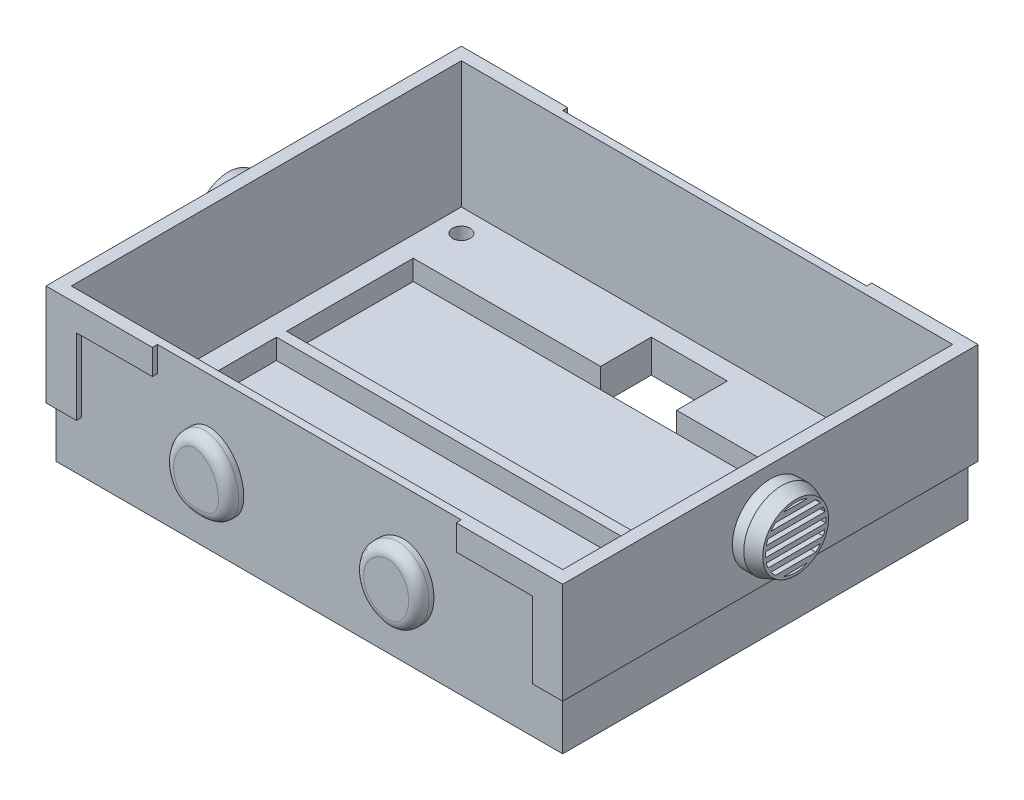
SolidWorks part; units mm, degrees
ref_plane "Plan de face" through (0, 0, 0) normal (0, 0, 1) x (1, 0, 0)
ref_plane "Plan de dessus" through (0, 0, 0) normal (0, 1, 0) x (1, 0, 0)
ref_plane "Plan de droite" through (0, 0, 0) normal (1, 0, 0) x (0, 0, -1)
sketch "Esquisse1" plane through (0, 0, 0) normal (0, 1, 0) x (1, 0, 0)
  line L1 (0, 0) -> (100, 0)
  line L2 (0, 0) -> (0, 80)
  line L3 (0, 80) -> (100, 80)
  line L4 (100, 0) -> (100, 80)
  line L13 (42.5, 75) -> (57.5, 75)
  line L14 (42.5, 75) -> (42.5, 65)
  line L15 (42.5, 65) -> (57.5, 65)
  line L16 (57.5, 75) -> (57.5, 65)
  dimension "D1" = 80
  dimension "D2" = 100
  dimension "D11" = 15
  dimension "D12" = 10
  dimension "D13" = 42.5
  dimension "D14" = 5
extrude "Boss.-Extru.2" add sketch "Esquisse1" along normal blind 5
sketch "Esquisse2" plane through (0, 5, 0) normal (0, 1, 0) x (1, 0, 0)
  line L0 (1.5, 10.5) -> (1.5, 1.5)
  line L1 (0, 80) -> (100, 80)
  line L2 (0, 80) -> (0, 68.5)
  line L3 (0, 0) -> (100, 0)
  line L4 (100, 80) -> (100, 0)
  line L5 (1.5, 78.5) -> (98.5, 78.5)
  line L6 (1.5, 78.5) -> (1.5, 69.5)
  line L7 (1.5, 1.5) -> (98.5, 1.5)
  line L8 (98.5, 78.5) -> (98.5, 1.5)
  line L9 (1.5, 10.5) -> (1.5, 69.5)
  line L10 (0, 68.5) -> (0, 13)
  line L18 (0, 13) -> (0, 0)
  dimension "D1" = 1.5
  dimension "D2" = 1.5
  dimension "D3" = 1.5
  dimension "D4" = 1.5
  dimension "D7" = 9
extrude "Boss.-Extru.3" add sketch "Esquisse2" along normal blind 25
sketch "Esquisse9" plane through (0, 0, 0) normal (0, -1, 0) x (1, 0, 0)
  line L0 (100, 0) -> (100, -80) construction
  line L1 (89, -2) -> (11, -2)
  line L2 (98, -11) -> (98, -69)
  line L3 (89, -78) -> (11, -78)
  line L4 (2, -11) -> (2, -69)
  line L5 (0, 0) -> (100, 0) construction
  line L6 (0, -80) -> (0, 0) construction
  line L7 (100, -80) -> (0, -80) construction
  line L9 (57.5, -65) -> (42.5, -65)
  line L10 (57.5, -65) -> (57.5, -75)
  line L11 (57.5, -75) -> (42.5, -75)
  line L12 (42.5, -65) -> (42.5, -75)
  line L15 (98, -11) -> (89, -11)
  line L16 (89, -2) -> (89, -11)
  line L19 (2, -11) -> (11, -11)
  line L20 (11, -2) -> (11, -11)
  line L23 (98, -69) -> (89, -69)
  line L24 (89, -78) -> (89, -69)
  line L27 (2, -69) -> (11, -69)
  line L28 (11, -78) -> (11, -69)
  dimension "D1" = 2
  dimension "D2" = 2
  dimension "D3" = 2
  dimension "D4" = 2
  dimension "D5" = 9
  dimension "D6" = 9
  dimension "D7" = 9
  dimension "D8" = 9
  dimension "D9" = 9
  dimension "D10" = 9
  dimension "D11" = 9
  dimension "D12" = 9
extrude "Boss.-Extru.5" add sketch "Esquisse9" along normal blind 1.5
sketch "Esquisse11" plane through (0, 5, 0) normal (0, 1, 0) x (1, 0, 0)
  line L1 (76.5, 65) -> (5.5, 65)
  line L2 (76.5, 60) -> (76.5, 40)
  line L3 (76.5, 40) -> (5.5, 40)
  line L5 (1.5, 1.5) -> (98.5, 1.5) construction
  line L6 (76.5, 38) -> (5.5, 38)
  line L7 (76.5, 33) -> (76.5, 13)
  line L8 (76.5, 13) -> (5.5, 13)
  line L10 (5.5, 65) -> (5.5, 40)
  line L11 (5.5, 13) -> (5.5, 38)
  line L15 (76.5, 65) -> (84.5, 65)
  line L19 (76.5, 60) -> (84.5, 60)
  line L20 (84.5, 65) -> (84.5, 60)
  line L21 (76.5, 38) -> (84.5, 38)
  line L23 (76.5, 33) -> (84.5, 33)
  line L24 (84.5, 38) -> (84.5, 33)
  dimension "D2" = 71
  dimension "D3" = 25
  dimension "D4" = 25
  dimension "D5" = 11.5
  dimension "D6" = 2
  dimension "D7" = 71
  dimension "D8" = 8
  dimension "D9" = 8
  dimension "D10" = 5
  dimension "D11" = 5
extrude "Enlèv. mat.-Extru.4" cut sketch "Esquisse11" against normal blind 4
sketch "Esquisse12" plane through (0, 5, 0) normal (0, 1, 0) x (1, 0, 0)
  line L0 (1.5, 78.5) -> (98.5, 78.5) construction
  line L1 (1.5, 1.5) -> (1.5, 78.5) construction
  line L2 (98.5, 78.5) -> (98.5, 1.5) construction
  line L3 (98.5, 1.5) -> (1.5, 1.5) construction
  line L4 (1.5, 1.5) -> (1.5, 78.5) construction
  circle A0 centre (6, 74) radius 1.75
  circle A1 centre (94, 74) radius 1.75
  circle A2 centre (94, 6) radius 1.75
  circle A3 centre (6, 6) radius 1.75
  dimension "D1" = 3.5
  dimension "D2" = 4.5
  dimension "D3" = 4.5
  dimension "D4" = 3.5
  dimension "D5" = 4.5
  dimension "D6" = 4.5
  dimension "D7" = 3.5
  dimension "D8" = 4.5
  dimension "D9" = 4.5
  dimension "D10" = 3.5
  dimension "D11" = 4.5
  dimension "D12" = 4.5
extrude "Enlèv. mat.-Extru.5" cut sketch "Esquisse12" against normal blind 10
fillet "Congé1" radius 10 2 edges at (84.5, 1, -62.5) (84.5, 1, -35.5)
sketch "Esquisse13" plane through (0, 0, 0) normal (0, 0, 1) x (1, 0, 0)
  line L0 (100, 30) -> (100, 0) construction
  line L1 (5, 10) -> (0, 10)
  line L2 (5, 10) -> (5, 25)
  line L3 (2.889, 30) -> (0, 30)
  line L4 (0, 10) -> (0, 30)
  line L5 (2.889, 30) -> (20, 30)
  line L7 (5, 25) -> (20, 25)
  line L8 (20, 30) -> (20, 25)
  line L9 (100, 10) -> (95, 10)
  line L10 (100, 10) -> (100, 30)
  line L11 (100, 30) -> (96.2257, 30)
  line L12 (95, 10) -> (95, 25)
  line L13 (0, 30) -> (100, 30) construction
  line L15 (96.2257, 30) -> (80, 30)
  line L17 (95, 25) -> (80, 25)
  line L18 (80, 30) -> (80, 25)
  dimension "D1" = 15
  dimension "D2" = 15
  dimension "D3" = 5
  dimension "D4" = 5
  dimension "D5" = 5
  dimension "D6" = 5
  dimension "D7" = 15
  dimension "D8" = 15
extrude "Boss.-Extru.6" add sketch "Esquisse13" along normal blind 1
sketch "Esquisse14" plane through (0, 0, -80) normal (0, 0, -1) x (-1, 0, 0)
  line L0 (-100, 30) -> (-100, 10)
  line L1 (-100, 30) -> (-100, 0) construction
  line L2 (-100, 10) -> (-95, 10)
  line L3 (-95, 10) -> (-95, 25)
  line L4 (-95, 25) -> (-80, 25)
  line L5 (-80, 25) -> (-80, 30)
  line L6 (-100, 30) -> (0, 30) construction
  line L7 (-80, 30) -> (-100, 30)
  line L8 (0, 30) -> (-20, 30)
  line L9 (-20, 30) -> (-20, 25)
  line L10 (-20, 25) -> (-5, 25)
  line L11 (-5, 25) -> (-5, 10)
  line L12 (-5, 10) -> (0, 10)
  line L13 (0, 30) -> (0, 0) construction
  line L14 (0, 10) -> (0, 30)
  dimension "D1" = 5
  dimension "D2" = 5
  dimension "D3" = 15
  dimension "D4" = 15
  dimension "D5" = 5
  dimension "D6" = 5
  dimension "D7" = 15
  dimension "D8" = 15
extrude "Boss.-Extru.7" add sketch "Esquisse14" along normal blind 1
sketch "Esquisse15" plane through (0, 0, 0) normal (-1, 0, 0) x (0, 0, 1)
  line L1 (-81, 30) -> (1, 30)
  line L2 (-81, 30) -> (-81, 10)
  line L3 (-81, 10) -> (1, 10)
  line L4 (1, 30) -> (1, 10)
extrude "Boss.-Extru.8" add sketch "Esquisse15" along normal blind 1
sketch "Esquisse16" plane through (100, 0, 0) normal (1, 0, 0) x (0, 0, -1)
  line L1 (-1, 30) -> (81, 30)
  line L2 (-1, 30) -> (-1, 10)
  line L3 (-1, 10) -> (81, 10)
  line L4 (81, 30) -> (81, 10)
extrude "Boss.-Extru.9" add sketch "Esquisse16" along normal blind 1
sketch "Esquisse17" plane through (0, 0, 0) normal (0, 0, 1) x (1, 0, 0)
  spline S0 degree 3 poles (38.1572, 7.8996) (30.5982, 6.4396) (26.5322, 7.7088) (23.9055, 11.5653) (24.0124, 17.1886) (29.3528, 22.2382) (37.068, 18.4959) (38.1572, 7.8996) (30.5982, 6.4396) (26.5322, 7.7088) knots -0.526062 -0.383052 -0.132187 0 0.105176 0.163659 0.330821 0.473938 0.616948 0.867813 1 1.105176 1.163659 1.330821 only from (30.308, 6.8948) to (30.308, 6.8948)
  spline S1 degree 3 poles (74.7762, 9.9599) (69.1945, 5.7934) (61.8135, 8.4606) (60.8681, 17.8505) (68.5681, 22.4656) (75.3269, 17.6132) (74.7762, 9.9599) (69.1945, 5.7934) (61.8135, 8.4606) knots -0.439073 -0.312677 -0.087479 0 0.172788 0.372419 0.560927 0.687323 0.912521 1 1.172788 1.372419 1.560927 only from (70.0415, 6.9485) to (70.0415, 6.9485)
extrude "Boss.-Extru.10" add sketch "Esquisse17" along normal blind 3
fillet "Congé2" radius 2 2 edges
sketch "Esquisse18" plane through (-1, 0, 0) normal (-1, 0, 0) x (0, 0, 1)
  line L0 (1, 10) -> (1, 30) construction
  line L2 (1, 30) -> (-81, 30) construction
  circle A0 centre (-40, 20) radius 7.5
  dimension "D1" = 15
  dimension "D2" = 41
  dimension "D3" = 10
extrude "Boss.-Extru.11" add sketch "Esquisse18" along normal blind 5
sketch "Esquisse19" plane through (-6, 0, 0) normal (-1, 0, 0) x (0, 0, 1)
  line L1 (-44.8734, 23.5) -> (-35.1266, 23.5)
  line L3 (-45.4544, 22.5) -> (-34.5456, 22.5)
  line L5 (-45.8095, 21.5) -> (-34.1905, 21.5)
  line L7 (-45.9791, 20.5) -> (-34.0209, 20.5)
  line L9 (-45.9791, 19.5) -> (-34.0209, 19.5)
  line L11 (-45.8095, 18.5) -> (-34.1905, 18.5)
  line L13 (-45.4544, 17.5) -> (-34.5456, 17.5)
  line L15 (-44.8734, 16.5) -> (-35.1266, 16.5)
  line L17 (-43.9686, 15.5) -> (-36.0314, 15.5)
  line L19 (-42.3979, 14.5) -> (-37.6021, 14.5)
  line L21 (-42.3979, 25.5) -> (-37.6021, 25.5)
  line L23 (-43.9686, 24.5) -> (-36.0314, 24.5)
  arc A0 (-43.9686, 24.5) -> (-44.8734, 23.5) centre (-40, 20) ccw
  circle A1 centre (-40, 20) radius 7.5 construction
  arc A3 (-37.6021, 25.5) -> (-42.3979, 25.5) centre (-40, 20) ccw
  arc A4 (-45.4544, 22.5) -> (-45.8095, 21.5) centre (-40, 20) ccw
  arc A5 (-35.1266, 23.5) -> (-36.0314, 24.5) centre (-40, 20) ccw
  arc A6 (-34.1905, 21.5) -> (-34.5456, 22.5) centre (-40, 20) ccw
  arc A7 (-45.9791, 20.5) -> (-45.9791, 19.5) centre (-40, 20) ccw
  arc A8 (-45.8095, 18.5) -> (-45.4544, 17.5) centre (-40, 20) ccw
  arc A9 (-34.0209, 19.5) -> (-34.0209, 20.5) centre (-40, 20) ccw
  arc A10 (-34.5456, 17.5) -> (-34.1905, 18.5) centre (-40, 20) ccw
  arc A11 (-44.8734, 16.5) -> (-43.9686, 15.5) centre (-40, 20) ccw
  arc A12 (-42.3979, 14.5) -> (-37.6021, 14.5) centre (-40, 20) ccw
  arc A13 (-36.0314, 15.5) -> (-35.1266, 16.5) centre (-40, 20) ccw
  dimension "D1" = 12
  dimension "D20" = 0.5
  dimension "D21" = 0.5
  dimension "D22" = 2.5
  dimension "D23" = 2.5
  dimension "D24" = 4.5
  dimension "D25" = 4.5
extrude "Enlèv. mat.-Extru.6" cut sketch "Esquisse19" against normal blind 1
sketch "Esquisse20" plane through (101, 0, 0) normal (1, 0, 0) x (0, 0, -1)
  line L1 (81, 10) -> (81, 30) construction
  line L3 (81, 30) -> (-1, 30) construction
  circle A0 centre (40, 20) radius 7.5
  dimension "D1" = 15
  dimension "D2" = 41
  dimension "D3" = 10
extrude "Boss.-Extru.12" add sketch "Esquisse20" along normal blind 5
sketch "Esquisse21" plane through (106, 0, 0) normal (1, 0, 0) x (0, 0, -1)
  line L1 (35.1266, 23.5) -> (44.8734, 23.5)
  line L3 (34.5456, 22.5) -> (45.4544, 22.5)
  line L5 (34.1905, 21.5) -> (45.8095, 21.5)
  line L7 (34.0209, 20.5) -> (45.9791, 20.5)
  line L9 (34.0209, 19.5) -> (45.9791, 19.5)
  line L11 (34.1905, 18.5) -> (45.8095, 18.5)
  line L13 (34.5456, 17.5) -> (45.4544, 17.5)
  line L15 (35.1266, 16.5) -> (44.8734, 16.5)
  line L17 (36.0314, 15.5) -> (43.9686, 15.5)
  line L19 (37.6021, 14.5) -> (42.3979, 14.5)
  line L21 (37.6021, 25.5) -> (42.3979, 25.5)
  line L23 (36.0314, 24.5) -> (43.9686, 24.5)
  arc A0 (36.0314, 24.5) -> (35.1266, 23.5) centre (40, 20) ccw
  circle A2 centre (40, 20) radius 7.5 construction
  arc A3 (42.3979, 25.5) -> (37.6021, 25.5) centre (40, 20) ccw
  arc A4 (34.5456, 22.5) -> (34.1905, 21.5) centre (40, 20) ccw
  arc A5 (44.8734, 23.5) -> (43.9686, 24.5) centre (40, 20) ccw
  arc A6 (45.8095, 21.5) -> (45.4544, 22.5) centre (40, 20) ccw
  arc A7 (34.0209, 20.5) -> (34.0209, 19.5) centre (40, 20) ccw
  arc A8 (34.1905, 18.5) -> (34.5456, 17.5) centre (40, 20) ccw
  arc A9 (45.9791, 19.5) -> (45.9791, 20.5) centre (40, 20) ccw
  arc A10 (45.4544, 17.5) -> (45.8095, 18.5) centre (40, 20) ccw
  arc A11 (35.1266, 16.5) -> (36.0314, 15.5) centre (40, 20) ccw
  arc A12 (37.6021, 14.5) -> (42.3979, 14.5) centre (40, 20) ccw
  arc A13 (43.9686, 15.5) -> (44.8734, 16.5) centre (40, 20) ccw
  dimension "D1" = 12
  dimension "D20" = 0.5
  dimension "D21" = 0.5
  dimension "D22" = 2.5
  dimension "D23" = 2.5
  dimension "D24" = 4.5
  dimension "D25" = 4.5
extrude "Enlèv. mat.-Extru.7" cut sketch "Esquisse21" against normal blind 1
chamfer "Chanfrein1" distance 1 angle 70 2 edges at (-6, 20, -32.5) (106, 20, -47.5)
